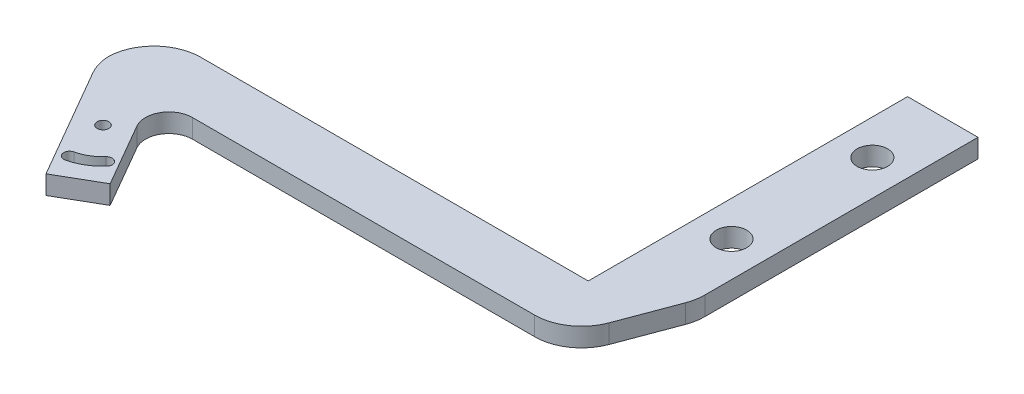
SolidWorks part; units mm, degrees
ref_plane "Front Plane" through (0, 0, 0) normal (0, 0, 1) x (1, 0, 0)
ref_plane "Top Plane" through (0, 0, 0) normal (0, 1, 0) x (1, 0, 0)
ref_plane "Right Plane" through (0, 0, 0) normal (1, 0, 0) x (0, 0, -1)
sketch "Sketch1" plane through (0, 0, 0) normal (0, 1, 0) x (1, 0, 0)
  line L0 (0, 0) -> (85.297, 0) construction
  line L1 (170.594, 30) -> (0, 30) construction
  line L2 (170.594, 30) -> (170.594, -30) construction
  line L3 (0, 30) -> (0, -30) construction
  line L4 (170.594, -30) -> (0, -30) construction
  line L5 (0, 0) -> (170.594, 0) construction
  line L6 (85.297, 30) -> (85.297, -30) construction
  line L7 (163.094, -50) -> (170.594, -30)
  line L8 (170.594, 30) -> (155.594, 30)
  line L9 (170.594, 30) -> (170.594, -30)
  line L10 (170.594, -30) -> (155.594, -30)
  line L11 (155.594, 30) -> (155.594, -30)
  line L12 (163.094, -30) -> (163.094, 30) construction
  line L13 (170.594, 0) -> (155.594, 0) construction
  line L14 (163.094, -30) -> (63.094, -30)
  line L15 (163.094, -30) -> (163.094, -50)
  line L16 (163.094, -50) -> (63.094, -50)
  line L17 (63.094, -30) -> (63.094, -50)
  line L18 (113.094, -50) -> (113.094, -30) construction
  line L19 (163.094, -40) -> (63.094, -40) construction
  line L20 (40, 0) -> (74.9241, -60.4904) construction
  line L25 (86.7543, -70.9808) -> (71.7543, -45)
  line L26 (86.7543, -70.9808) -> (78.094, -75.9808)
  line L27 (163.094, -50) -> (163.094, -30)
  line L28 (71.7543, -45) -> (63.094, -50)
  line L29 (78.094, -75.9808) -> (63.094, -50)
  line L30 (67.4241, -47.5) -> (82.4241, -73.4808) construction
  line L31 (79.2543, -57.9904) -> (70.594, -62.9904) construction
  circle A0 centre (0, 0) radius 55 construction
  point P97 (163.094, 0)
  point P100 (113.094, -40)
  dimension "D1" = 110
  dimension "D2" = 60
  dimension "D4" = 15
  dimension "D5" = 100
  dimension "D6" = 20
  dimension "D7" = 40
  dimension "D8" = 120
  dimension "D9" = 30
  dimension "D10" = 10
extrude "Boss-Extrude1" add sketch "Sketch1" along normal blind 4 contours L8 L11 L10 L9 | L10 L15 L7 | L28 L25 L16 L15 L10 L14 L17 | L28 L25 L26 L29 region at (165.594, 0, 36.6667) region at (113.7276, 0, 39.878) region at (163.094, 0, 0)
sketch "Sketch2" plane through (0, 0, 0) normal (0, 1, 0) x (1, 0, 0)
  line L0 (63.094, -30) -> (63.094, -50) construction
  line L1 (155.594, -30) -> (63.094, -30)
  line L2 (155.594, -30) -> (155.594, -38)
  line L3 (155.594, -38) -> (63.094, -38)
  line L4 (63.094, -30) -> (63.094, -38)
  line L5 (109.344, -38) -> (109.344, -30) construction
  line L6 (155.594, -34) -> (63.094, -34) construction
  point P36 (109.344, -34)
  dimension "D1" = 8
extrude "Cut-Extrude1" cut sketch "Sketch2" along normal through all
sketch "Sketch3" plane through (0, 4, 0) normal (0, 1, 0) x (1, 0, 0)
  line L0 (78.094, -75.9808) -> (82.4241, -73.4808) construction
  line L1 (78.094, -75.9808) -> (70.844, -63.4234) construction
  line L2 (82.4241, -73.4808) -> (75.1741, -60.9234) construction
  line L3 (70.844, -63.4234) -> (75.1741, -60.9234) construction
  line L4 (86.7543, -70.9808) -> (78.094, -75.9808) construction
  circle A0 centre (75.1741, -60.9234) radius 1.25
  circle A1 centre (79.9241, -69.1506) radius 1.25
  dimension "D1" = 2.5
  dimension "D2" = 9.5
  dimension "D3" = 5
  dimension "D4" = 5
extrude "Cut-Extrude2" cut sketch "Sketch3" against normal through all
sketch "Sketch4" plane through (0, 4, 0) normal (0, 1, 0) x (1, 0, 0)
  line L0 (163.094, 30) -> (163.094, -38) construction
  line L1 (170.594, 30) -> (155.594, 30) construction
  circle A0 centre (163.094, 15) radius 3.25
  circle A1 centre (163.094, -15) radius 3.25
  dimension "D1" = 6.5
  dimension "D2" = 30
  dimension "D3" = 15
extrude "Cut-Extrude3" cut sketch "Sketch4" against normal through all
fillet "Fillet1" radius 10 4 edges at (63.094, 2, 50) (63.094, 2, 38) (163.094, 2, 50) (170.594, 2, 30)
fillet "Fillet2" radius 5 1 edges at (74.641, 2, 50)
sketch "Sketch5" plane through (0, 4, 0) normal (0, 1, 0) x (1, 0, 0)
  line L0 (83.1629, -68.1165) -> (81.3051, -66.4437) construction
  line L1 (77.5924, -71.3979) -> (77.03, -68.9619) construction
  line L2 (78.094, -75.9808) -> (64.4338, -52.3205) construction
  arc A0 (83.1629, -68.1165) -> (77.5924, -71.3979) centre (75.1741, -60.9234) cw
  arc A1 (81.3051, -66.4437) -> (77.03, -68.9619) centre (75.1741, -60.9234) cw
  arc A2 (83.1629, -68.1165) -> (81.3051, -66.4437) centre (82.234, -67.2801) ccw
  arc A3 (77.03, -68.9619) -> (77.5924, -71.3979) centre (77.3112, -70.1799) ccw
  dimension "D2" = 8.25
  dimension "D1" = 2.5
  dimension "D3" = 35
  dimension "D4" = 17
extrude "Cut-Extrude4" cut sketch "Sketch5" against normal through all
